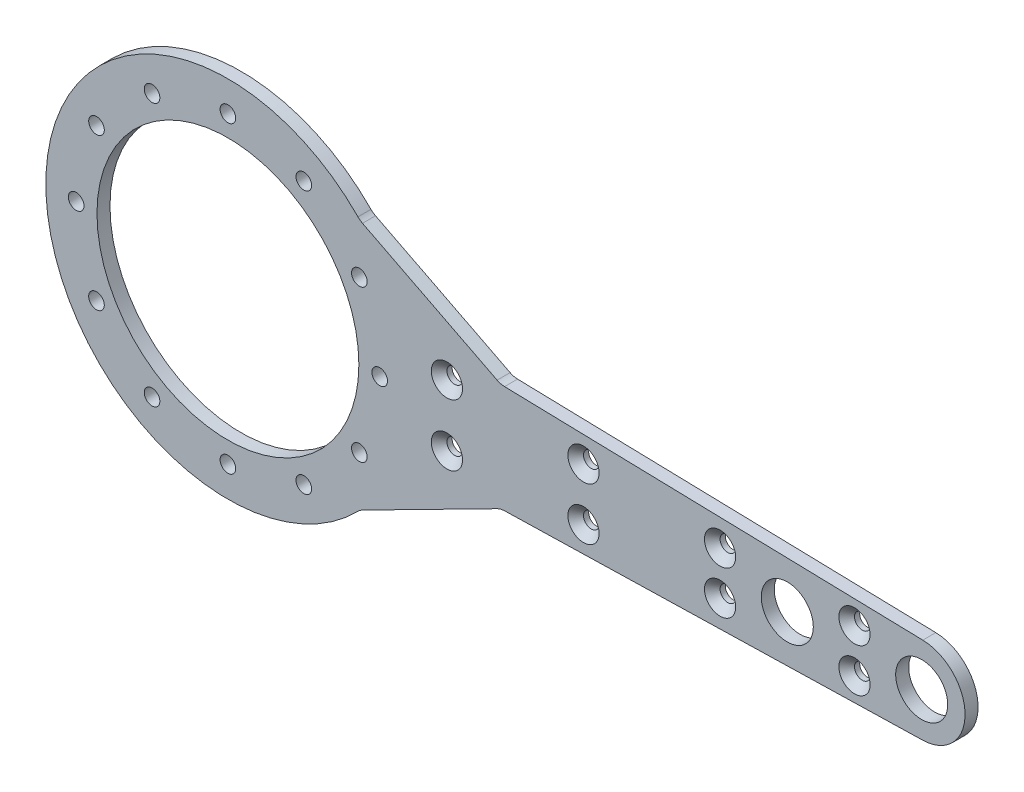
SolidWorks part; units mm, degrees
material "Hexcel AS4C (3000 Filaments)"
ref_plane "Front Plane" through (0, 0, 0) normal (0, 0, 1) x (1, 0, 0)
ref_plane "Top Plane" through (0, 0, 0) normal (0, 1, 0) x (1, 0, 0)
ref_plane "Right Plane" through (0, 0, 0) normal (1, 0, 0) x (0, 0, -1)
sketch "Sketch1" plane through (0, 0, 0) normal (0, 0, 1) x (1, 0, 0)
  line L0 (19.9687, 6.5) -> (80.1248, 4.9984)
  line L1 (19.9687, -6.5) -> (80.1248, -4.9984)
  line L2 (19.9687, 6.5) -> (19.9687, -6.5) construction
  circle A0 centre (0, 0) radius 15.1
  arc A1 (19.9687, 6.5) -> (19.9687, -6.5) centre (0, 0) ccw
  circle A2 centre (64.5, 0) radius 3
  circle A3 centre (80, 0) radius 3
  arc A4 (80.1248, -4.9984) -> (80.1248, 4.9984) centre (80, 0) ccw
  circle A5 centre (0, 0) radius 17.5 construction
  dimension "D1" = 30.2
  dimension "D4" = 6
  dimension "D3" = 21
  dimension "D5" = 80
  dimension "D7" = 5
  dimension "D8" = 35
  dimension "D2" = 15.5
  dimension "D6" = 13
extrude "Boss-Extrude1" add sketch "Sketch1" along normal blind 1.5
hole_wizard "Dégagement M1.62" positions "Sketch5" profile "Sketch4" hole size "M1.6" standard "Din"
sketch "Sketch5" plane through (0, 0, 1.5) normal (0, 0, 1) x (1, 0, 0)
  circle A0 centre (0, 0) radius 17.5
  point P0 (0, 17.5)
  dimension "D1" = 35
sketch "Sketch4" plane through (0, 17.5, 1.5) normal (1, 0, 0) x (0, -1, 0)
  line L0 (0, 0) -> (0, 11.5)
  line L1 (0, 11.5) -> (0.9, 11.5)
  line L2 (0.9, 11.5) -> (0.9, 0)
  line L5 (0.9, 0) -> (0, 0)
  line L10 (0, 11.5) -> (-0.9, 11.5) construction
  line L11 (0, -6.35) -> (0, 107.95) construction
  dimension "Hole Dia." = 1.8
  dimension "Hole Depth" = 11.5
  dimension "Drill Angle" = 180
pattern_circular "CirPattern1" count 12 over 360 about axis through (0, 0, 0) along (0, 0, 1) of "Dégagement M1.62"
hole_wizard "M2 Clearance Hole2" [suppressed] positions "Sketch7" profile "Sketch6" hole size "M2" standard "DIN"
sketch "Sketch7" plane through (0, 0, 1.5) normal (0, 0, 1) x (1, 0, 0)
  line L6 (0, 0) -> (80, 0) construction
  line L8 (64.5, 0) -> (64.5, -10.138) construction
  line L10 (80, 0) -> (80, -7.973) construction
  point P283 (56.75, 0)
  point P285 (72.25, 0)
  dimension "D1" = 7.75
sketch "Sketch6" plane through (56.75, 0, 1.5) normal (1, 0, 0) x (0, -1, 0)
  line L0 (0, 0) -> (0, 11.5)
  line L1 (0, 11.5) -> (1.2, 11.5)
  line L2 (1.2, 11.5) -> (1.2, 0)
  line L5 (1.2, 0) -> (0, 0)
  line L10 (0, 11.5) -> (-1.2, 11.5) construction
  line L11 (0, -6.35) -> (0, 107.95) construction
  dimension "Hole Dia." = 2.4
  dimension "Hole Depth" = 11.5
  dimension "Drill Angle" = 180
chamfer "Chamfer2" distance 7 angle 45 2 edges at (19.9687, -6.5, 0.75) (19.9687, 6.5, 0.75) first distance on face at (-0.5156, 0, 0.75)
fillet "Fillet4" radius 2 4 edges at (31.4459, -6.2135, 0.75) (15.2179, -14.4712, 0.75) (15.2179, 14.4712, 0.75) (31.4459, 6.2135, 0.75)
sketch "Sketch8" plane through (0, 0, 1.5) normal (0, 0, 1) x (1, 0, 0)
  line L1 (51, -2.5) -> (22, -2.5)
  line L2 (53, -0.5) -> (53, 0.5)
  line L3 (51, 2.5) -> (22, 2.5)
  line L4 (20, -0.5) -> (20, 0.5)
  line L5 (53, -2.5) -> (20, 2.5) construction
  line L6 (53, 2.5) -> (20, -2.5) construction
  arc A0 (51, -2.5) -> (53, -0.5) centre (51, -0.5) ccw
  arc A1 (22, -2.5) -> (20, -0.5) centre (22, -0.5) cw
  arc A2 (22, 2.5) -> (20, 0.5) centre (22, 0.5) ccw
  arc A3 (53, 0.5) -> (51, 2.5) centre (51, 0.5) ccw
  point P0 (36.5, 0)
  dimension "D4" = 2
  dimension "D1" = 20
  dimension "D2" = 53
  dimension "D3" = 5
hole_wizard "Dégagement M1.61" positions "Sketch11" profile "Sketch10" hole size "M1.6" standard "Din"
sketch "Sketch11" plane through (0, 0, 1.5) normal (0, 0, 1) x (1, 0, 0)
  circle A2 centre (64.5, 0) radius 3 construction
  circle A3 centre (64.5, 0) radius 3 construction
  point P0 (56.75, 2.5)
  point P1 (72.25, 2.5)
  point P3 (72.25, -2.5)
  point P5 (56.75, -2.5)
  dimension "D4" = 2.5
  dimension "D6" = 2.5
  dimension "D1" = 15.5
  dimension "D2" = 7.75
  dimension "D3" = 2.5
  dimension "D5" = 2.5
  dimension "D7" = 7.75
  dimension "D8" = 7.75
sketch "Sketch10" plane through (56.75, 2.5, 1.5) normal (1, 0, 0) x (0, -1, 0)
  line L0 (0, 0) -> (0, 11.5)
  line L1 (0, 11.5) -> (0.9, 11.5)
  line L2 (0.9, 11.5) -> (0.9, 0)
  line L5 (0.9, 0) -> (0, 0)
  line L10 (0, 11.5) -> (-0.9, 11.5) construction
  line L11 (0, -6.35) -> (0, 107.95) construction
  dimension "Diamètre du perçage" = 1.8
  dimension "Profondeur du perçage" = 11.5
  dimension "Angle de pointe" = 180
chamfer "Chamfer3" distance 0.9 angle 45 4 edges at (57.65, -2.5, 1.5) (73.15, -2.5, 1.5) (73.15, 2.5, 1.5) (57.65, 2.5, 1.5)
sketch "Esquisse1" plane through (0, 0, 1.5) normal (0, 0, 1) x (1, 0, 0)
  line L0 (0, 0) -> (25.2518, 3.5489) construction
  line L1 (0, 0) -> (25.5, 0) construction
  line L2 (0, 0) -> (25.2518, -3.5489) construction
  circle A0 centre (0, 0) radius 21.5 construction
  circle A1 centre (0, 0) radius 25.5 construction
  circle A2 centre (25.2518, 3.5489) radius 0.9
  circle A3 centre (25.2518, -3.5489) radius 0.9
  dimension "D1" = 43
  dimension "D2" = 4
  dimension "D5" = 1.8
  dimension "D6" = 1.8
  dimension "D3" = 8
  dimension "D4" = 8
extrude "Enlèv. mat.-Extru.1" cut sketch "Esquisse1" against normal blind 10
chamfer "Chanfrein1" distance 0.9 angle 45 2 edges at (26.1518, -3.5489, 1.5) (26.1518, 3.5489, 1.5)
sketch "Esquisse2" plane through (0, 0, 1.5) normal (0, 0, 1) x (1, 0, 0)
  line L0 (25.2518, 3.5489) -> (56.75, 2.5) construction
  line L1 (25.2518, -3.5489) -> (56.75, -2.5) construction
  circle A0 centre (41.0009, 3.0245) radius 0.9
  circle A1 centre (41.0009, -3.0245) radius 0.9
  dimension "D1" = 1.8
  dimension "D2" = 1.8
extrude "Enlèv. mat.-Extru.2" cut sketch "Esquisse2" against normal blind 10
chamfer "Chanfrein2" distance 0.9 angle 45 2 edges at (41.9009, -3.0245, 1.5) (41.9009, 3.0245, 1.5)
